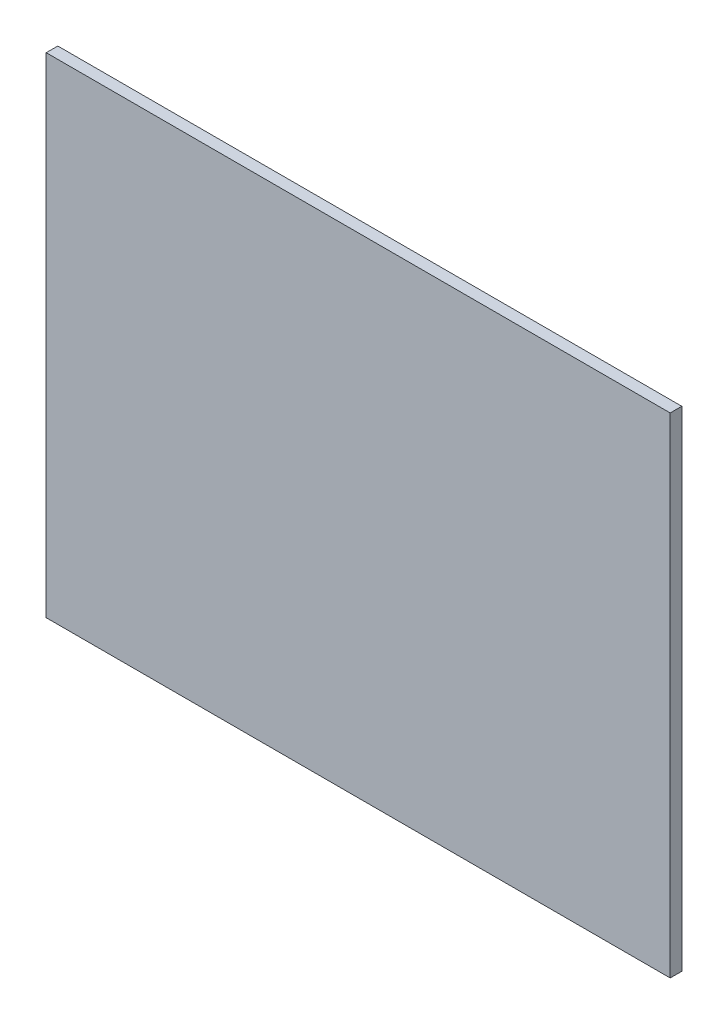
SolidWorks part; units mm, degrees
ref_plane "Спереди" through (0, 0, 0) normal (0, 0, 1) x (1, 0, 0)
ref_plane "Сверху" through (0, 0, 0) normal (0, 1, 0) x (1, 0, 0)
ref_plane "Справа" through (0, 0, 0) normal (1, 0, 0) x (0, 0, -1)
sketch "Эскиз1" plane through (0, 0, 0) normal (0, 0, 1) x (1, 0, 0)
  line L5 (19.5, 16.9) -> (19.5, -16.9)
  line L6 (23.5, 17) -> (23.5, 14.8) construction
  line L14 (23.4, -14.8) -> (23.4, -16.9)
  line L15 (23.4, -16.9) -> (-23.6, -16.9)
  line L16 (-23.6, -16.9) -> (-23.6, 16.9)
  line L17 (-23.6, 16.9) -> (23.5, 16.9)
  line L19 (19.5, -16.9) -> (-23.6, -16.9)
  line L20 (-23.6, -16.9) -> (-23.6, 16.9)
  line L21 (-23.6, 16.9) -> (19.5, 16.9)
  dimension "D1" = 0.1
  dimension "D2" = 4
  dimension "D3" = 33.8
  dimension "D4" = 43.1
extrude "Бобышка-Вытянуть1" add sketch "Эскиз1" along normal blind 0.8 from offset 0.6
